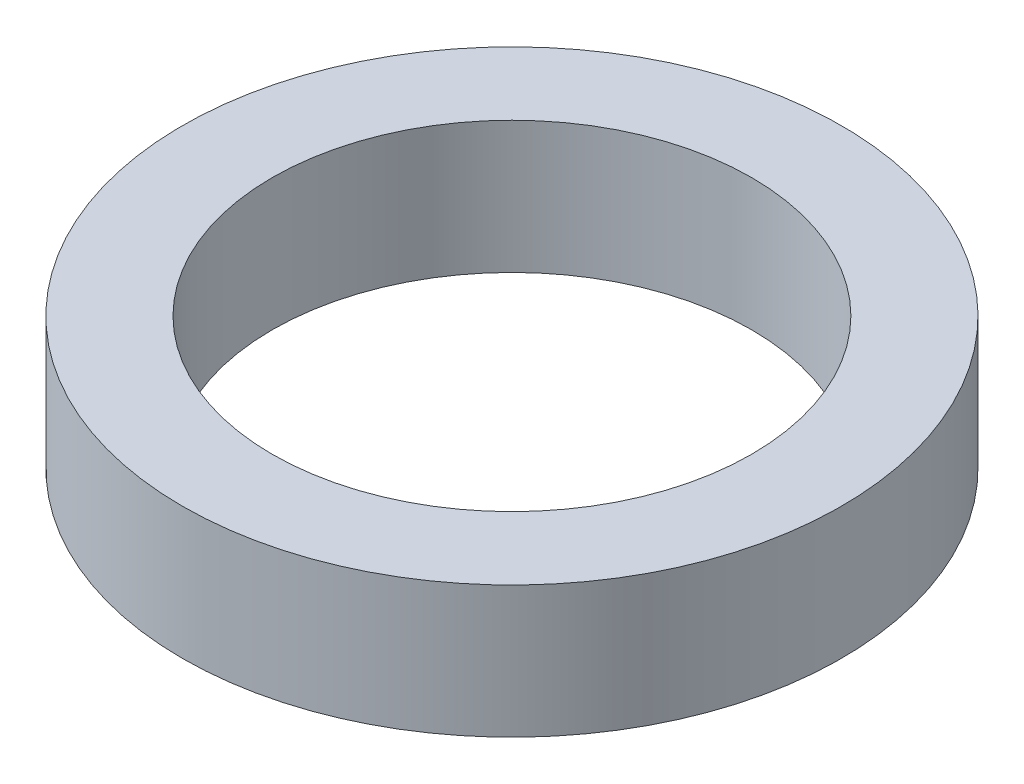
SolidWorks part; units mm, degrees
ref_plane "Front Plane" through (0, 0, 0) normal (0, 0, 1) x (1, 0, 0)
ref_plane "Top Plane" through (0, 0, 0) normal (0, 1, 0) x (1, 0, 0)
ref_plane "Right Plane" through (0, 0, 0) normal (1, 0, 0) x (0, 0, -1)
sketch "Sketch1" plane through (0, 0, 0) normal (0, 1, 0) x (1, 0, 0)
  circle A0 centre (0, 0) radius 55
  dimension "FLANGE_OD" = 110
extrude "Boss-Extrude1" add sketch "Sketch1" along normal blind 22
sketch "Sketch2" plane through (0, 0, 0) normal (0, 1, 0) x (1, 0, 0)
  circle A0 centre (0, 0) radius 40
  dimension "BORE_D" = 80
extrude "Cut-Extrude1" cut sketch "Sketch2" along normal through all
sketch "Sketch3" plane through (0, 22, 0) normal (0, 1, 0) x (1, 0, 0)
  circle A0 centre (0, 0) radius 25.4733 construction
  circle A1 centre (-25.4733, 0) radius 2.4986
  dimension "BOLT_D" = 4.9972
  dimension "BOLT_PCD" = 50.9467
extrude "Cut-Extrude2" cut sketch "Sketch3" against normal blind 15.6467 rebuild error yes
pattern_circular "CirPattern1" count 6 over 360 rebuild error yes
